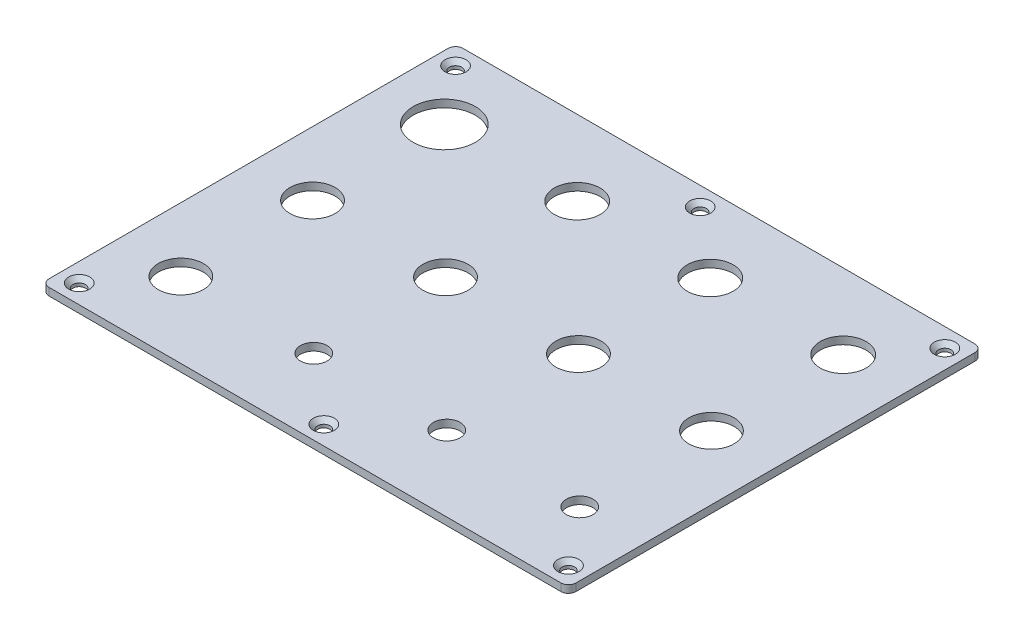
SolidWorks part; units mm, degrees
ref_plane "Front Plane" through (0, 0, 0) normal (0, 0, 1) x (1, 0, 0)
ref_plane "Top Plane" through (0, 0, 0) normal (0, 1, 0) x (1, 0, 0)
ref_plane "Right Plane" through (0, 0, 0) normal (1, 0, 0) x (0, 0, -1)
sketch "Bottom Plate" plane through (0, 0, 0) normal (0, 1, 0) x (1, 0, 0)
  line L1 (0, 0) -> (-140, 0)
  line L2 (0, 0) -> (0, 110)
  line L3 (0, 110) -> (-140, 110)
  line L4 (-140, 0) -> (-140, 110)
  dimension "D1" = 140
  dimension "D2" = 110
extrude "Bottom Plate EXT" add sketch "Bottom Plate" along normal blind 2
sketch "Middle Row" plane through (0, 2, 0) normal (0, 1, 0) x (1, 0, 0)
  line L0 (-140, 110) -> (-140, 0) construction
  line L1 (-140, 55) -> (0, 55) construction
  line L2 (0, 0) -> (0, 110) construction
  circle A0 centre (-123, 55) radius 6
  circle A1 centre (-87.6667, 55) radius 6
  circle A2 centre (-52.3333, 55) radius 6
  circle A3 centre (-17, 55) radius 6
  dimension "D1" = 12
  dimension "D2" = 35.3333
  dimension "D6" = 35.3333
  dimension "D3" = 35.3333
  dimension "D4" = 17
extrude "Middle Row Cut" cut sketch "Middle Row" against normal through all
sketch "Top Row" plane through (0, 2, 0) normal (0, 1, 0) x (1, 0, 0)
  line L0 (0, 0) -> (0, 110) construction
  line L1 (-140, 110) -> (-140, 0) construction
  line L2 (-123, 90) -> (-17, 90) construction
  line L3 (0, 110) -> (-140, 110) construction
  line L7 (-58.4333, 90) -> (-17, 90) construction
  circle A0 centre (-123, 90) radius 8.25
  circle A1 centre (-87.6667, 90) radius 6.1
  circle A2 centre (-52.3333, 90) radius 6.1
  circle A3 centre (-17, 90) radius 6.1
  dimension "D1" = 16.5
  dimension "D2" = 20
  dimension "D7" = 12.2
  dimension "D8" = 35.3333
  dimension "D3" = 17
  dimension "D4" = 35.3333
  dimension "D5" = 106
  dimension "D6" = 17
extrude "Top Row Cut" cut sketch "Top Row" against normal through all
sketch "Bottom Row" plane through (0, 2, 0) normal (0, 1, 0) x (1, 0, 0)
  line L0 (-140, 0) -> (0, 0) construction
  line L1 (-140, 110) -> (-140, 0) construction
  circle A0 centre (-87.6667, 20) radius 3.55
  circle A1 centre (-52.3333, 20) radius 3.55
  circle A2 centre (-17, 20) radius 3.55
  circle A5 centre (-123, 20) radius 6
  circle A6 centre (-123, 55) radius 6 construction
  dimension "D1" = 7.1
  dimension "D2" = 20
  dimension "D3" = 35.3333
  dimension "D4" = 35.3333
  dimension "D5" = 35.3333
  dimension "D6" = 17
extrude "Bottom Row Cut" cut sketch "Bottom Row" against normal through all
sketch "Plate Screws" plane through (0, 2, 0) normal (0, 1, 0) x (1, 0, 0)
  line L0 (0, 110) -> (-140, 110) construction
  line L1 (-140, 110) -> (-140, 0) construction
  line L2 (-140, 0) -> (0, 0) construction
  line L3 (0, 0) -> (0, 110) construction
  line L4 (-70, 110) -> (-70, 59.8221) construction
  line L5 (0, 55) -> (-30.2044, 55) construction
  circle A0 centre (-135, 105) radius 1.65
  circle A1 centre (-5, 105) radius 1.65
  circle A2 centre (-5, 5) radius 1.65
  circle A3 centre (-135, 5) radius 1.65
  circle A4 centre (-70, 105) radius 1.65
  circle A5 centre (-70, 5) radius 1.65
  dimension "D1" = 3.3
  dimension "D2" = 5
  dimension "D3" = 5
  dimension "D4" = 5
  dimension "D5" = 5
extrude "Plate Screws Cut" cut sketch "Plate Screws" against normal through all
sketch "Plate Screw Head" plane through (0, 2, 0) normal (0, 1, 0) x (1, 0, 0)
  line L0 (-70, 110) -> (-70, 73.7034) construction
  line L1 (0, 110) -> (-140, 110) construction
  line L2 (0, 55) -> (-52.6177, 55) construction
  line L3 (0, 0) -> (0, 110) construction
  circle A0 centre (-135, 105) radius 2.8
  circle A1 centre (-5, 105) radius 2.8
  circle A2 centre (-5, 5) radius 2.8
  circle A3 centre (-135, 5) radius 2.8
  circle A4 centre (-70, 105) radius 2.8
  circle A5 centre (-70, 5) radius 2.8
  dimension "D1" = 5.6
extrude "Plate Screw Head Cut" cut sketch "Plate Screw Head" against normal blind 2 draft 45
fillet "Fillet1" radius 2 1 edges at (-140, 1, -110) type face fillet first side face at (-140, 1, -55) second side face at (-70, 1, -110)
fillet "Fillet2" radius 2 1 edges at (0, 1, -110) type face fillet first side face at (-69, 1, -110) second side face at (0, 1, -55)
fillet "Fillet3" radius 2 1 edges at (0, 1, 0) type face fillet first side face at (0, 1, -54) second side face at (-70, 1, 0)
fillet "Fillet4" radius 2 1 edges at (-140, 1, 0) type face fillet first side face at (-71, 1, 0) second side face at (-140, 1, -54)
equation "\"SPACER_THIRD\" = \"D5@Top Row\" / 3mm"
equation "\"D4@Top Row\"=\"SPACER_THIRD\""
equation "\"D8@Top Row\"=\"SPACER_THIRD\""
equation "\"SPACER_SIDE\"= 17mm"
equation "\"D3@Top Row\" = \"SPACER_SIDE\""
equation "\"D6@Top Row\" = \"SPACER_SIDE\""
equation "\"D4@Middle Row\" = \"SPACER_SIDE\""
equation "\"D2@Middle Row\"=\"SPACER_THIRD\""
equation "\"D3@Middle Row\"=\"SPACER_THIRD\""
equation "\"D6@Middle Row\"=\"SPACER_THIRD\""
equation "\"D6@Bottom Row\" = \"SPACER_SIDE\""
equation "\"D5@Bottom Row\"=\"SPACER_THIRD\""
equation "\"D3@Bottom Row\"=\"SPACER_THIRD\""
equation "\"D4@Bottom Row\"=\"SPACER_THIRD\""
equation "\"SPACER_TOP\"= 20mm"
equation "\"D2@Top Row\"=\"SPACER_TOP\""
equation "\"D2@Bottom Row\"=\"SPACER_TOP\""
